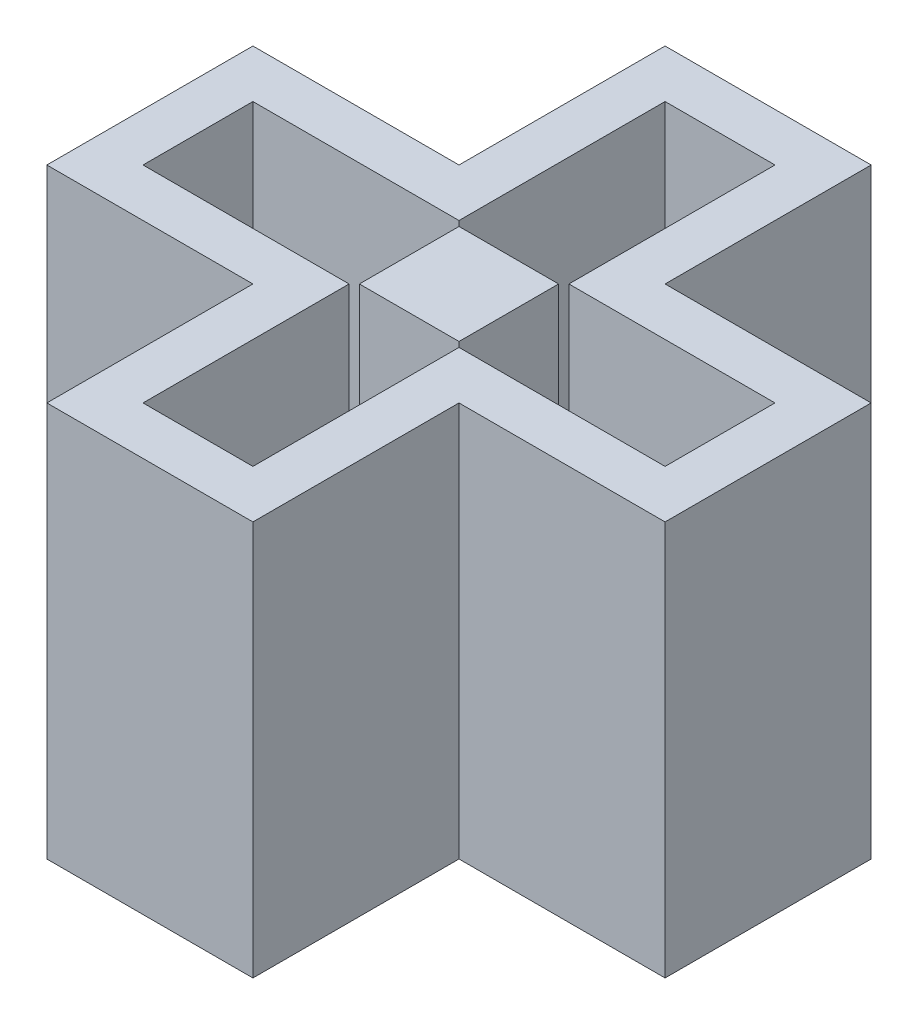
SolidWorks part; units mm, degrees
ref_plane "Front Plane" through (0, 0, 0) normal (0, 0, 1) x (1, 0, 0)
ref_plane "Top Plane" through (0, 0, 0) normal (0, 1, 0) x (1, 0, 0)
ref_plane "Right Plane" through (0, 0, 0) normal (1, 0, 0) x (0, 0, -1)
sketch "Sketch1" plane through (0, 0, 0) normal (0, 1, 0) x (1, 0, 0)
  line L0 (-3, 3) -> (-3, 9)
  line L1 (-3, 9) -> (3, 9)
  line L2 (3, 9) -> (3, 3)
  line L3 (3, 3) -> (9, 3)
  line L4 (9, 3) -> (9, -3)
  line L5 (9, -3) -> (3, -3)
  line L6 (3, -3) -> (3, -9)
  line L7 (3, -9) -> (-3, -9)
  line L8 (-3, -9) -> (-3, -3)
  line L9 (-3, -3) -> (-9, -3)
  line L10 (-9, -3) -> (-9, 3)
  line L11 (-9, 3) -> (-3, 3)
  point P13 (-9, 0)
  point P14 (0, 9)
  dimension "D1" = 6
  dimension "D2" = 6
extrude "Boss-Extrude1" add sketch "Sketch1" along normal blind 1.5
sketch "Sketch3" plane through (0, 1.5, 0) normal (0, 1, 0) x (1, 0, 0)
  line L0 (-1.6, 1.6) -> (-7.6, 1.6)
  line L1 (-7.6, 1.6) -> (-7.6, -1.6)
  line L2 (-7.6, -1.6) -> (-1.6, -1.6)
  line L3 (-1.6, -1.6) -> (-1.6, -7.6)
  line L4 (-1.6, -7.6) -> (1.6, -7.6)
  line L5 (1.6, -7.6) -> (1.6, -1.6)
  line L6 (1.6, -1.6) -> (7.6, -1.6)
  line L7 (7.6, -1.6) -> (7.6, 1.6)
  line L8 (7.6, 1.6) -> (1.6, 1.6)
  line L9 (1.6, 1.6) -> (1.6, 7.6)
  line L10 (1.6, 7.6) -> (-1.6, 7.6)
  line L11 (-1.6, 7.6) -> (-1.6, 1.6)
  line L12 (-3, 3) -> (-9, 3)
  line L13 (-9, 3) -> (-9, -3)
  line L14 (-9, -3) -> (-3, -3)
  line L15 (-3, -3) -> (-3, -9)
  line L16 (-3, -9) -> (3, -9)
  line L17 (3, -9) -> (3, -3)
  line L18 (3, -3) -> (9, -3)
  line L19 (9, -3) -> (9, 3)
  line L20 (9, 3) -> (3, 3)
  line L21 (3, 3) -> (3, 9)
  line L22 (3, 9) -> (-3, 9)
  line L23 (-3, 9) -> (-3, 3)
  line L24 (-3, 3) -> (-9, 3)
  line L25 (-9, 3) -> (-9, -3)
  line L26 (-9, -3) -> (-3, -3)
  line L27 (-3, -3) -> (-3, -9)
  line L28 (-3, -9) -> (3, -9)
  line L29 (3, -9) -> (3, -3)
  line L30 (3, -3) -> (9, -3)
  line L31 (9, -3) -> (9, 3)
  line L32 (9, 3) -> (3, 3)
  line L33 (3, 3) -> (3, 9)
  line L34 (3, 9) -> (-3, 9)
  line L35 (-3, 9) -> (-3, 3)
  dimension "D2" = 1.4
extrude "Boss-Extrude5" add sketch "Sketch3" along normal blind 10
sketch "Sketch2" plane through (0, 1.5, 0) normal (0, 1, 0) x (1, 0, 0)
  line L1 (-1.45, 1.45) -> (1.45, 1.45)
  line L2 (-1.45, 1.45) -> (-1.45, -1.45)
  line L3 (-1.45, -1.45) -> (1.45, -1.45)
  line L4 (1.45, 1.45) -> (1.45, -1.45)
  point P4 (-1.45, 0)
  point P5 (0, 1.45)
  dimension "D1" = 2.9
extrude "Boss-Extrude2" add sketch "Sketch2" along normal blind 10
sketch "Sketch4" [suppressed] plane through (0, 12, 0) normal (0, 1, 0) x (1, 0, 0)
  line L1 (-11.5, 3.5) -> (-3.5, 3.5)
  line L2 (-11.5, 3.5) -> (-11.5, -3.5)
  line L3 (-11.5, -3.5) -> (-3.5, -3.5)
  line L4 (-3.5, 3.5) -> (-3.5, -3.5)
extrude "Cut-Extrude1" [suppressed] cut sketch "Sketch4" against normal through all
sketch "Sketch5" [suppressed] plane through (0, 12, 0) normal (0, 1, 0) x (1, 0, 0)
  line L0 (-1.4, 1.4) -> (-1.4, -1.4) construction
  line L1 (-3.5, 1.7) -> (-1.7, 1.7)
  line L2 (-3.5, 1.7) -> (-3.5, -1.7)
  line L3 (-3.5, -1.7) -> (-1.7, -1.7)
  line L4 (-1.7, 1.7) -> (-1.7, 1.4)
  line L5 (-1.4, 1.4) -> (-1.7, 1.4)
  line L6 (-1.4, 1.4) -> (-1.4, -1.4)
  line L7 (-1.4, -1.4) -> (-1.7, -1.4)
  line L9 (1.4, 1.4) -> (-1.4, 1.4) construction
  line L10 (-1.4, -1.4) -> (1.4, -1.4) construction
  line L11 (-1.7, -1.4) -> (-1.7, -1.7)
extrude "Boss-Extrude6" [suppressed] add sketch "Sketch5" against normal blind 10
sketch "Sketch6" [suppressed] plane through (0, 12, 0) normal (0, 1, 0) x (1, 0, 0)
  line L1 (-3.5, 11.5) -> (3.5, 11.5)
  line L2 (-3.5, 11.5) -> (-3.5, 3.5)
  line L3 (-3.5, 3.5) -> (3.5, 3.5)
  line L4 (3.5, 11.5) -> (3.5, 3.5)
extrude "Cut-Extrude2" [suppressed] cut sketch "Sketch6" against normal through all
sketch "Sketch7" [suppressed] plane through (0, 12, 0) normal (0, 1, 0) x (1, 0, 0)
  line L0 (1.4, 1.4) -> (-1.7, 1.4) construction
  line L1 (-1.7, 3.5) -> (-1.7, 1.4) construction
  line L2 (-1.7, 3.5) -> (1.7, 3.5) construction
  line L3 (1.4, 1.4) -> (-1.7, 1.4)
  line L4 (-1.7, 3.5) -> (-1.7, 1.4)
  line L5 (-1.7, 3.5) -> (1.7, 3.5)
  line L8 (1.7, 3.5) -> (1.7, 1.7)
  line L9 (1.7, 1.7) -> (1.4, 1.7)
  line L10 (1.4, 1.7) -> (1.4, 1.4)
extrude "Boss-Extrude7" [suppressed] add sketch "Sketch7" against normal blind 10
sketch "Sketch8" [suppressed] plane through (0, 12, 0) normal (0, 1, 0) x (1, 0, 0)
  line L1 (3.5, 3.5) -> (11.5, 3.5)
  line L2 (3.5, 3.5) -> (3.5, -3.5)
  line L3 (3.5, -3.5) -> (11.5, -3.5)
  line L4 (11.5, 3.5) -> (11.5, -3.5)
extrude "Cut-Extrude3" [suppressed] cut sketch "Sketch8" against normal through all
sketch "Sketch9" [suppressed] plane through (0, 12, 0) normal (0, 1, 0) x (1, 0, 0)
  line L0 (1.4, -1.4) -> (1.4, 1.4) construction
  line L1 (3.5, 1.7) -> (1.7, 1.7) construction
  line L2 (3.5, 1.7) -> (3.5, -1.7) construction
  line L3 (1.7, -1.7) -> (3.5, -1.7) construction
  line L4 (1.4, -1.4) -> (1.4, 1.4)
  line L5 (3.5, 1.7) -> (1.7, 1.7)
  line L6 (3.5, 1.7) -> (3.5, -1.7)
  line L7 (1.7, -1.7) -> (3.5, -1.7)
  line L8 (1.4, 1.4) -> (1.7, 1.4)
  line L9 (1.7, 1.4) -> (1.7, 1.7)
  line L10 (1.4, -1.4) -> (1.7, -1.4)
  line L11 (1.7, -1.4) -> (1.7, -1.7)
extrude "Boss-Extrude8" [suppressed] add sketch "Sketch9" against normal blind 10
equation "\"mdfWidth\"= 3"
equation "\"cellSide\"= 180"
equation "\"mazeHeight\" = 50"
equation "\"slitHeight\"= 10"
equation "\"gripWidth\"= 6"
equation "\"wallThickness\"= 1.5"
equation "\"slitWidth\" = \"wallThickness\""
equation "\"D1@Sketch1\"= \"mdfWidth\" + 2 * \"wallThickness\""
equation "\"D2@Sketch1\"=\"gripWidth\""
equation "\"D1@Boss-Extrude1\"= \"wallThickness\""
equation "\"D1@Boss-Extrude2\"= \"slitHeight\""
equation "\"D2@Sketch3\"=\"wallThickness\" - \"jeu\""
equation "\"D1@Boss-Extrude5\"= \"slitHeight\""
equation "\"jeu\"= 0.1"
equation "\"D1@Sketch2\"=\"mdfWidth\"- \"jeu\""
equation "\"D1@Boss-Extrude6\"= \"slitHeight\""
equation "\"D1@Boss-Extrude7\"= \"slitHeight\""
equation "\"D1@Boss-Extrude8\"= \"slitHeight\""
